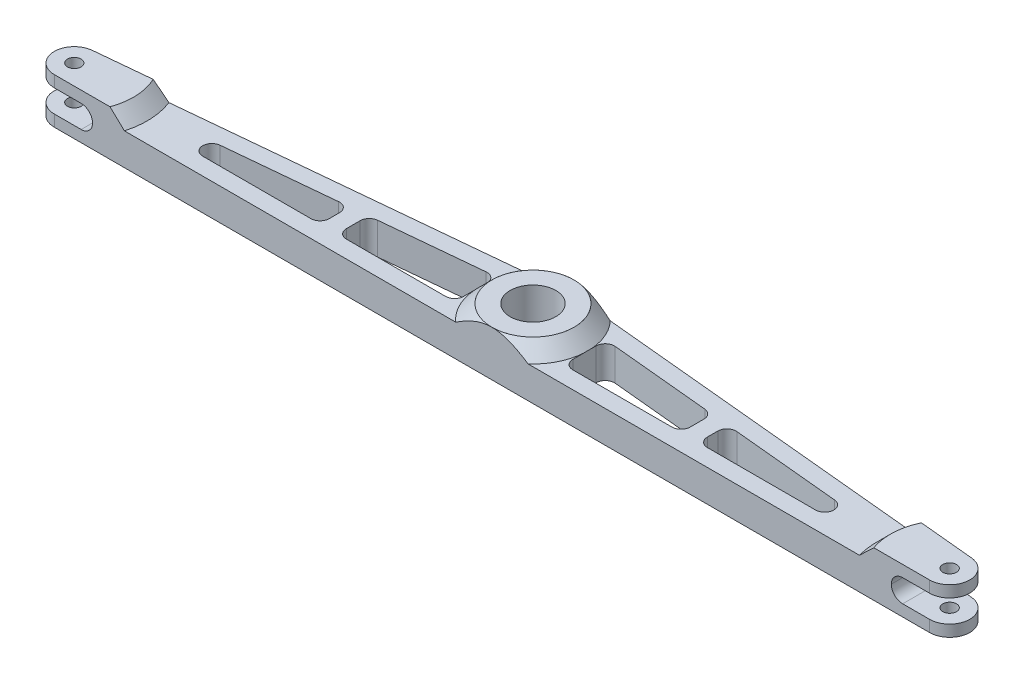
SolidWorks part; units mm, degrees
note: '?' marks a value the reader was unsure of.
material "6061-T6 (SS)"
ref_plane "Front Plane" through (0, 0, 0) normal (0, 0, 1) x (1, 0, 0)
ref_plane "Top Plane" through (0, 0, 0) normal (0, 1, 0) x (1, 0, 0)
ref_plane "Right Plane" through (0, 0, 0) normal (1, 0, 0) x (0, 0, -1)
sketch "Sketch1" plane through (0, 0, 0) normal (0, 1, 0) x (1, 0, 0)
  line L0 (0, 0) -> (-152.4, -7.3025) construction
  line L1 (0, 0) -> (152.4, -7.3025) construction
  line L2 (-152.4, -7.3025) -> (152.4, -7.3025) construction
  line L3 (-152.4, -14.2875) -> (152.4, -14.2875)
  line L4 (-153.0679, -0.3495) -> (-1.3661, 14.222)
  line L5 (153.0679, -0.3495) -> (1.3661, 14.222)
  arc A1 (-153.0679, -0.3495) -> (-152.4, -14.2875) centre (-152.4, -7.3025) ccw
  arc A2 (152.4, -14.2875) -> (153.0679, -0.3495) centre (152.4, -7.3025) ccw
  arc A3 (1.3661, 14.222) -> (-1.3661, 14.222) centre (0, 0) ccw
  circle A4 centre (0, 0) radius 14.2875 construction
  circle A5 centre (-152.4, -7.3025) radius 2.3813
  circle A6 centre (152.4, -7.3025) radius 2.3813
  dimension "D2" = 28.575
  dimension "D3" = 4.7625
  dimension "D4" = 6.985
  dimension "D1" = 304.8
extrude "Boss-Extrude1" add sketch "Sketch1" along normal mid plane 15.875
sketch "Sketch3" plane through (0, 7.9375, 0) normal (0, 1, 0) x (1, 0, 0)
  circle A0 centre (0, 0) radius 7.9375
  dimension "D1" = 15.875
extrude "Cut-Extrude2" cut sketch "Sketch3" against normal up to next
sketch "Sketch2" plane through (0, 0, 0) normal (0, 0, 1) x (1, 0, 0)
  line L0 (159.385, -7.9375) -> (159.385, 7.9375) construction
  line L1 (139.065, -3.9375) -> (159.385, -3.9375)
  line L2 (139.065, -3.9375) -> (139.065, 3.9375)
  line L3 (139.065, 3.9375) -> (159.385, 3.9375)
  line L4 (159.385, -3.9375) -> (159.385, 3.9375)
  line L5 (139.065, -3.9375) -> (159.385, 3.9375) construction
  line L6 (139.065, 3.9375) -> (159.385, -3.9375) construction
  line L7 (159.385, 7.9375) -> (152.4, 7.9375) construction
  point P0 (149.225, 0)
  point P7 (0, 0)
  dimension "D1" = 4
  dimension "D2" = 20.32
extrude "Cut-Extrude1" cut sketch "Sketch2" against normal through all both and the other way through all
sketch "Sketch4" plane through (0, 7.9375, 0) normal (0, 1, 0) x (1, 0, 0)
  line L0 (19, 6.5006) -> (19, -8.2875)
  line L6 (19, 6.5006) -> (59.8478, 2.577)
  line L7 (19, -8.2875) -> (59.8478, -8.2875)
  line L8 (65.8478, -8.2875) -> (106.6957, -8.2875)
  line L9 (65.8478, 2.0007) -> (106.9992, -1.952)
  line L10 (153.0679, -0.3495) -> (1.3661, 14.222) construction
  line L11 (59.8478, -8.2875) -> (59.8478, 2.577)
  line L12 (65.8478, 2.0007) -> (65.8478, -8.2875)
  line L14 (59.8478, 2.577) -> (60.4215, 8.5495) construction
  line L15 (59.8478, -8.2875) -> (59.8478, -14.2875) construction
  line L16 (-152.4, -14.2875) -> (152.4, -14.2875) construction
  line L17 (59.8478, -8.2875) -> (65.8478, -8.2875) construction
  arc A3 (106.9992, -1.952) -> (106.6957, -8.2875) centre (106.6957, -5.1125) cw
  point P8 (106.6196, -5.1089)
  dimension "D1" = 19
  dimension "D3" = 3.175
  dimension "D2" = 6
extrude "Cut-Extrude3" cut sketch "Sketch4" against normal up to next
sketch "Sketch7" plane through (0, 0, 0) normal (0, 0, 1) x (1, 0, 0)
  line L0 (106.6957, 7.9375) -> (106.6957, 3.1745)
  line L1 (-152.4, 7.9375) -> (152.4, 7.9375) construction
  line L2 (106.6957, 3.1745) -> (0, 3.1745)
  line L3 (0, 3.1745) -> (0, 7.9375)
  line L4 (0, 7.9375) -> (106.6957, 7.9375)
  point P4 (0, 0)
  point P7 (16.8792, 7.5)
  point P9 (198.8002, 7.9375)
  point P10 (132.6917, 7.9375)
  point P11 (-1.1103, 7.5)
  point P13 (191.3305, 7.9375)
  dimension "D3" = 4.763
extrude "Cut-Extrude4" cut sketch "Sketch7" against normal through all both and the other way through all
ref_axis "Axis1" through (152.4, 7.9375, 7.3025) along (0, -1, 0)?
ref_plane "Plane1" through (0, 0, 7.3025) normal (0, 0, 1) x (1, 0, 0)
sketch "Sketch10" plane through (0, 0, 7.3025) normal (0, 0, 1) x (1, 0, 0)
  line L0 (101.6157, 3.1745) -> (127, 3.1745)
  line L1 (127, 3.1745) -> (131.763, 7.9375)
  line L2 (106.6957, 7.9375) -> (152.4, 7.9375) construction
  line L3 (131.763, 7.9375) -> (101.6157, 7.9375)
  line L4 (101.6157, 7.9375) -> (101.6157, 3.1745)
  line L6 (152.4, 10.6134) -> (152.4, -0.6413) construction
  line L7 (152.4, 7.9375) -> (152.4, 3.9375) construction
  line L9 (106.6957, 3.1745) -> (106.6957, 7.9375) construction
  point P14 (183.1808, 2.4183)
  dimension "D1" = 45
  dimension "D2" = 25.4
  dimension "D3" = 5.08
revolve "Cut-Revolve2" cut sketch "Sketch10" angle 360 about L6
fillet "Fillet1" radius 3.175 6 edges at (19, -2.3815, 8.2875) (19, -2.3815, -6.5006) (59.8478, -2.3815, 8.2875) (59.8478, -2.3815, -2.577) (65.8478, -2.3815, 8.2875) (65.8478, -2.3815, -2.0007)
fillet "Fillet2" radius 3.9688 2 edges at (139.065, -3.9375, 6.646) (139.065, 3.9375, 6.646)
mirror "Mirror1" about plane through (0, 0, 0) normal (1, 0, 0) of "Fillet2", "Cut-Extrude4", "Cut-Extrude1", "Cut-Extrude3", "Fillet1", "Cut-Revolve2"
sketch "Sketch8" plane through (0, 3.1745, 0) normal (0, 1, 0) x (1, 0, 0)
  circle A0 centre (0, 0) radius 14.2875
  circle A1 centre (0, 0) radius 7.9375 construction
  circle A2 centre (0, 0) radius 7.9375
extrude "Boss-Extrude2" add sketch "Sketch8" along normal up to surface (4.763 mm away) up to face at (152.4, 7.9375, 9.6838)
chamfer "Chamfer2" distance 4.7625 angle 45 2 edges at (-14.2711, 3.1745, 0.6838) (14.2711, 3.1745, 0.6838)
